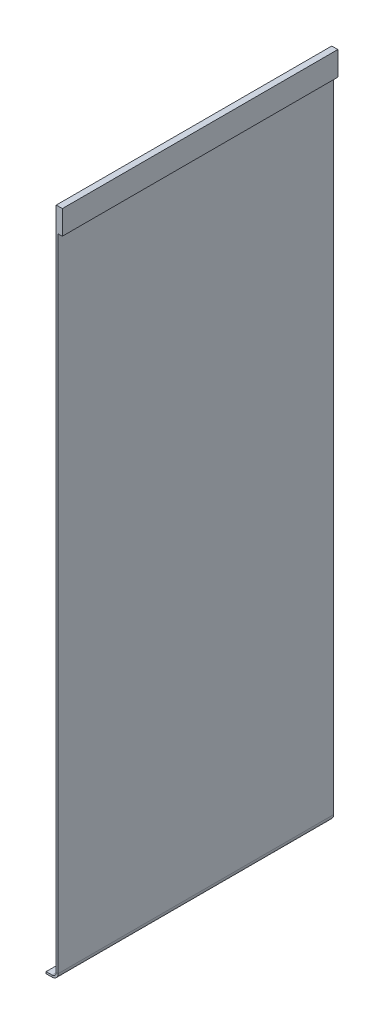
SolidWorks part; units mm, degrees
note: The reader was unsure of these and kept them because the rebuilt part matched: flange length of "Edge-Flange1".
material "Plain Carbon Steel"
ref_plane "Front Plane" through (0, 0, 0) normal (0, 0, 1) x (1, 0, 0)
ref_plane "Top Plane" through (0, 0, 0) normal (0, 1, 0) x (1, 0, 0)
ref_plane "Right Plane" through (0, 0, 0) normal (1, 0, 0) x (0, 0, -1)
sketch "Sketch1" plane through (0, 0, 0) normal (1, 0, 0) x (0, 0, -1)
  line L1 (0, 0) -> (73.025, 0)
  line L2 (0, 0) -> (0, 177.8)
  line L3 (0, 177.8) -> (73.025, 177.8)
  line L4 (73.025, 0) -> (73.025, 177.8)
  dimension "D1" = 73.025
  dimension "D2" = 177.8
base flange "Base-Flange1" sketch "Sketch1" thickness 0.508 reverse thickness direction no parameters "D1"=1.1112
sketch "Sketch2" plane through (0, 0, 0) normal (1, 0, 0) x (0, 0, -1)
  line L0 (73.025, 0) -> (73.025, 177.8) construction
  line L1 (0, 177.8) -> (73.025, 177.8)
  line L2 (0, 177.8) -> (0, 171.45)
  line L3 (0, 171.45) -> (73.025, 171.45)
  line L4 (73.025, 177.8) -> (73.025, 171.45)
  dimension "D1" = 6.35
extrude "Boss-Extrude1" add sketch "Sketch2" along normal blind 1.1112
edge flange "Edge-Flange1" sketch "Sketch5" flange angle 90 flange length 3.175 flange position material inside bend radius 1.1112 thickness 0.508 relief rectangular parameters "D6"=10
sketch "Sketch5" plane through (-0.508, 0, 0) normal (0, 1, 0) x (0, 0, -1)
  line L1 (73.025, 0) -> (0, 0) construction
  line L2 (0, 0) -> (0, 2.667)
  line L3 (0, 2.667) -> (73.025, 2.667)
  line L4 (73.025, 2.667) -> (73.025, 0)
  line L5 (73.025, 0) -> (0, 0)
bend "EdgeBend1" bend radius 1.1112 bend angle 90 parameters "D5"=1
sketch "Bend-Lines1" [suppressed] plane through (0, 0, 0) normal (0, 1, 0) x (1, 0, 0)
sketch "Bounding-Box1" [suppressed] plane through (0, 0, 0) normal (0, 1, 0) x (1, 0, 0)
sheet metal parameters "Sheet-Metal1" thickness 0.508 parameters "D1"=0.7366
flat pattern "Flat-Pattern1" [suppressed]
sketch "Bend-Lines2" plane through (0, 0, 0) normal (0, 1, 0) x (1, 0, 0)
sketch "Bounding-Box2" [suppressed] plane through (0, 0, 0) normal (0, 1, 0) x (1, 0, 0)
sheet metal parameters "Sheet-Metal2" thickness 0.508 parameters "D1"=0.7366
flat pattern "Flat-Pattern1"
sketch "Bend-Lines2" plane through (0, 0, 0) normal (0, 1, 0) x (1, 0, 0)
sketch3d "Bounding-Box2" [suppressed]
  line L0 (0, 146.05, 0) -> (0, 0, 0) construction
  line L1 (73.025, 146.05, 0) -> (73.025, 0, 0) construction
  line L2 (0, 146.05, 0) -> (73.025, 146.05, 0) construction
  line L3 (0, 0, 0) -> (73.025, 0, 0) construction
sheet metal parameters "Sheet-Metal3" thickness 0.508 parameters "D1"=0.7366
flat pattern "Flat-Pattern1" [suppressed]
sketch "Bend-Lines2" plane through (0, 0, 0) normal (0, 1, 0) x (1, 0, 0)
sketch3d "Bounding-Box2" [suppressed]
  line L0 (0, 146.05, 0) -> (0, 0, 0) construction
  line L1 (73.025, 146.05, 0) -> (73.025, 0, 0) construction
  line L2 (0, 146.05, 0) -> (73.025, 146.05, 0) construction
  line L3 (0, 0, 0) -> (73.025, 0, 0) construction
bend of the flat pattern "Flatten-<EdgeBend1>1"
